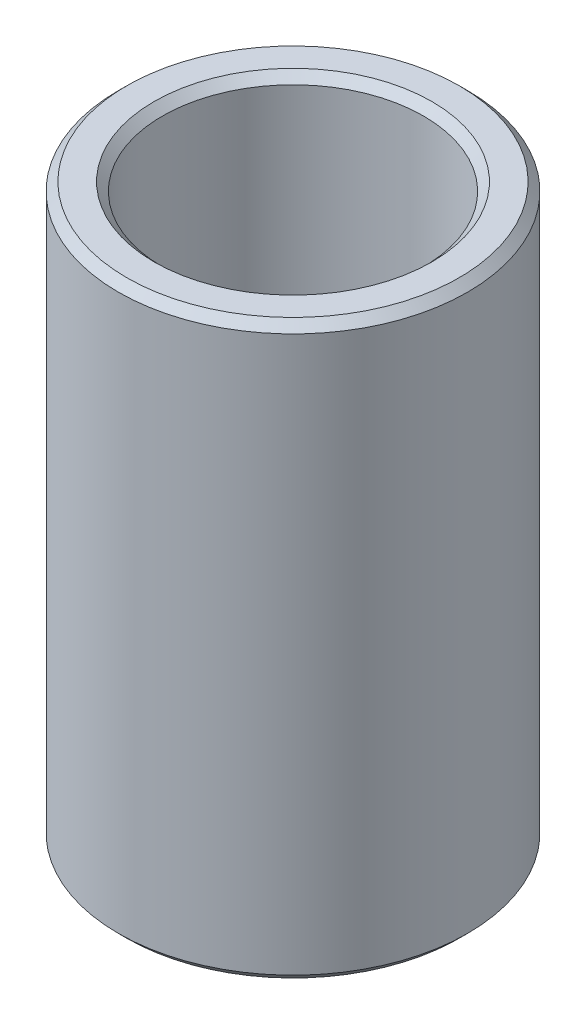
SolidWorks part; units mm, degrees
ref_plane "Front Plane" through (0, 0, 0) normal (0, 0, 1) x (1, 0, 0)
ref_plane "Top Plane" through (0, 0, 0) normal (0, 1, 0) x (1, 0, 0)
ref_plane "Right Plane" through (0, 0, 0) normal (1, 0, 0) x (0, 0, -1)
sketch "Sketch1" plane through (0, 0, 0) normal (0, 1, 0) x (1, 0, 0)
  circle A0 centre (0, 0) radius 25
  dimension "SLEEVE_OD" = 50
extrude "Boss-Extrude1" add sketch "Sketch1" along normal blind 81.9049
sketch "Sketch2" plane through (0, 0, 0) normal (0, 1, 0) x (1, 0, 0)
  circle A0 centre (0, 0) radius 18.6935
  dimension "BORE_D" = 37.3871
extrude "Cut-Extrude1" cut sketch "Sketch2" along normal through all
chamfer "Chamfer1" distance 1.1963 angle 45 4 edges at (0, 81.9049, 18.6935) (0, 0, 18.6935) (0, 0, 25) (0, 81.9049, 25)
